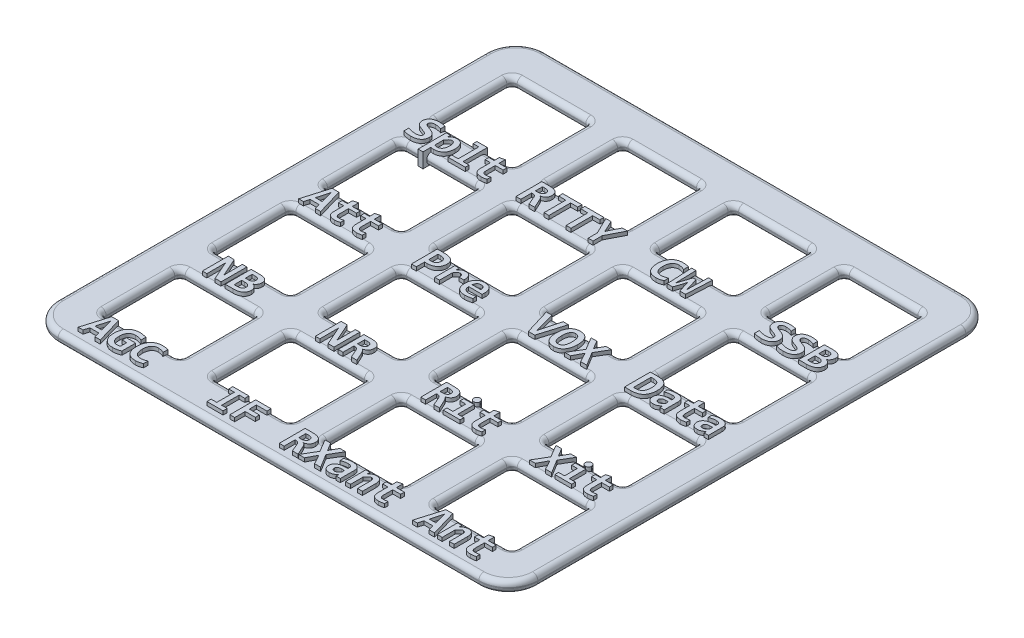
SolidWorks part; units mm, degrees
ref_plane "Front" through (0, 0, 0) normal (0, 0, 1) x (1, 0, 0)
ref_plane "Top" through (0, 0, 0) normal (0, 1, 0) x (1, 0, 0)
ref_plane "Right" through (0, 0, 0) normal (1, 0, 0) x (0, 0, -1)
sketch "Sketch1" plane through (0, 0, 0) normal (0, 1, 0) x (1, 0, 0)
  line L1 (-14.8807, -14.5355) -> (42.1193, -14.5355)
  line L2 (-18.8807, -18.5355) -> (-18.8807, -76.5355)
  line L3 (-14.8807, -80.5355) -> (42.1193, -80.5355)
  line L4 (46.1193, -18.5355) -> (46.1193, -76.5355)
  arc A0 (-14.8807, -14.5355) -> (-18.8807, -18.5355) centre (-14.8807, -18.5355) ccw
  arc A1 (46.1193, -18.5355) -> (42.1193, -14.5355) centre (42.1193, -18.5355) ccw
  arc A2 (42.1193, -80.5355) -> (46.1193, -76.5355) centre (42.1193, -76.5355) ccw
  arc A3 (-18.8807, -76.5355) -> (-14.8807, -80.5355) centre (-14.8807, -76.5355) ccw
  dimension "D1" = 65
  dimension "D2" = 66
extrude "main" add sketch "Sketch1" along normal blind 1.5
sketch "Sketch2" plane through (0, 1.5, 0) normal (0, 1, 0) x (1, 0, 0)
  line L0 (42.1193, -14.5355) -> (-14.8807, -14.5355) construction
  line L1 (-14.2307, -19.6855) -> (-3.5307, -19.6855)
  line L2 (-14.2307, -19.6855) -> (-14.2307, -30.3855)
  line L3 (-14.2307, -30.3855) -> (-3.5307, -30.3855)
  line L4 (-3.5307, -19.6855) -> (-3.5307, -30.3855)
  line L5 (-18.8807, -18.5355) -> (-18.8807, -76.5355) construction
  point P4 (-8.8807, -19.6855)
  dimension "D1" = 5.15
  dimension "D2" = 4.65
  dimension "D3" = 10.7
  dimension "D4" = 10.7
extrude "button hole 1" cut sketch "Sketch2" against normal through all
fillet "button fillet" radius 0.7 12 edges at (-8.8807, 0, 30.3855) (-8.8807, 1.5, 30.3855) (-8.8807, 0, 19.6855) (-8.8807, 1.5, 19.6855) (-3.5307, 0.75, 30.3855) (-3.5307, 0, 25.0355) (-3.5307, 0.75, 19.6855) (-3.5307, 1.5, 25.0355) (-14.2307, 0.75, 19.6855) (-14.2307, 0, 25.0355) (-14.2307, 0.75, 30.3855) (-14.2307, 1.5, 25.0355)
pattern_linear "buttons by 16" count 4 spacing 15 along (1, 0, 0) count 4 spacing 15 along (0, 0, 1) of "button fillet", "button hole 1"
fillet "outer edge fillet" radius 0.7 16 edges at (13.6193, 1.5, 14.5355) (13.6193, 0, 14.5355) (46.1193, 1.5, 47.5355) (46.1193, 0, 47.5355) (13.6193, 1.5, 80.5355) (13.6193, 0, 80.5355) (-18.8807, 1.5, 47.5355) (-18.8807, 0, 47.5355) (44.9477, 1.5, 15.7071) (44.9477, 1.5, 79.364) (-17.7092, 1.5, 79.364) (-17.7092, 1.5, 15.7071) (44.9477, 0, 15.7071) (44.9477, 0, 79.364) (-17.7092, 0, 79.364) (-17.7092, 0, 15.7071)
sketch "Lettering" plane through (0, 0, 0) normal (0, 1, 0) x (1, 0, 0)
  line L0 (45.4193, -49.1355) -> (-18.1807, -49.1355) construction
  line L1 (45.4783, -79.1355) -> (-16.5217, -79.1355) construction
  line L2 (45.4193, -76.5355) -> (45.4193, -18.5355) construction
  line L3 (-18.1807, -18.5355) -> (-18.1807, -76.5355) construction
  line L5 (45.4193, -64.1355) -> (-18.1807, -64.1355) construction
  line L6 (45.4193, -76.5355) -> (45.4193, -18.5355) construction
  line L7 (-18.1807, -18.5355) -> (-18.1807, -76.5355) construction
  line L8 (45.4193, -34.1355) -> (-18.1807, -34.1355) construction
  line L11 (-14.8807, -80.5355) -> (42.1193, -80.5355) construction
  text T0 "SSB" font "Consolas" height 3.5
  text T1 "CW" font "Consolas" height 3.5
  text T2 "RTTY" font "Consolas" height 3.5
  text T3 "Splt" font "Consolas" height 3.5
  text T4 "Xit" font "Consolas" height 3.5
  text T5 "Rit" font "Consolas" height 3.5
  text T6 "NB" font "Consolas" height 3.5
  text T7 "NR" font "Consolas" height 3.5
  text T8 "VOX" font "Consolas" height 3.5
  text T9 "RXant" font "Consolas" height 3.5
  text T10 "Pre" font "Consolas" height 3.5
  text T11 "AGC" font "Consolas" height 3.5
  text T12 "Att" font "Consolas" height 3.5
  text T13 "IF\r\n" font "Consolas" height 3.5
  text T14 "Ant" font "Consolas" height 3.5
  text T15 "Data" font "Consolas" height 3.5
  dimension "D1" = 46.4
  dimension "D2" = 16.4
  dimension "D3" = 1.4
  dimension "D4" = 31.4
extrude "lettering boss" add sketch "Lettering" along normal offset from surface (2 mm away) 0.5 up to face at (13.6193, 1.5, 47.5355) offset beyond the face yes
